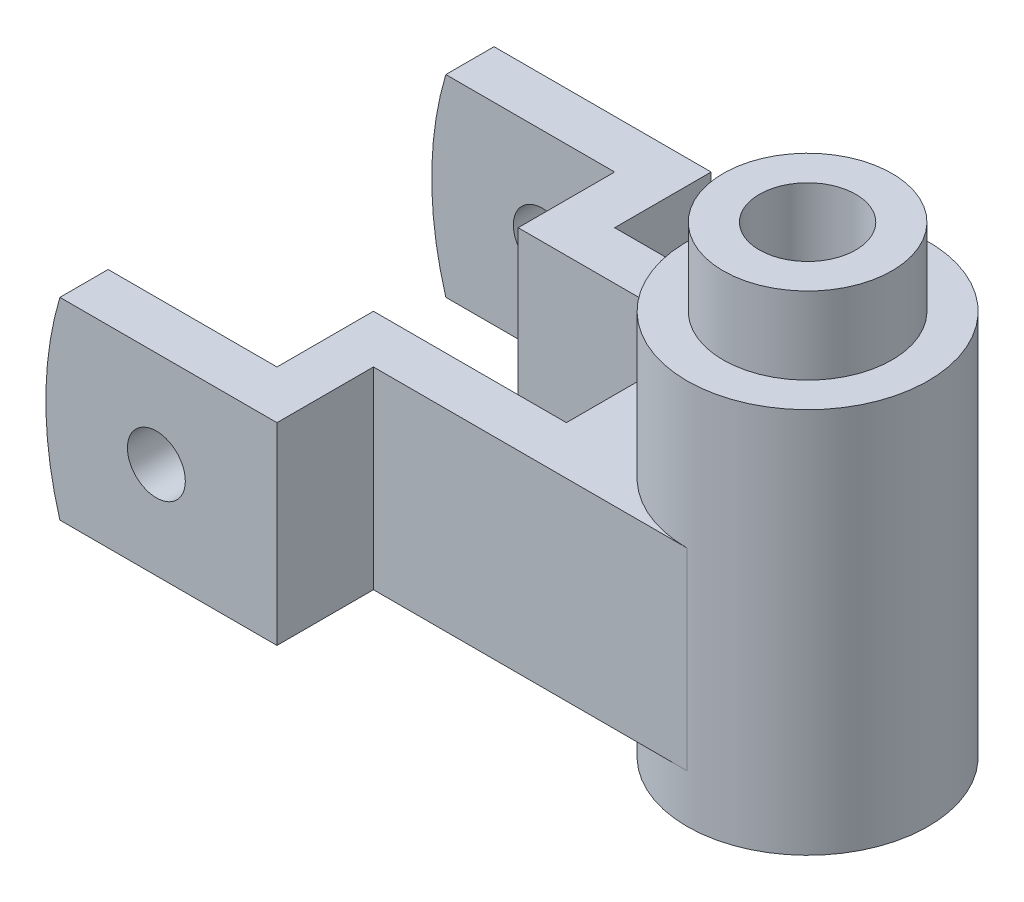
SolidWorks part; units mm, degrees
note: The reader was unsure of these and kept them because the rebuilt part matched: shared geometry of "Sketch2<3>".
ref_plane "Front Plane" through (0, 0, 0) normal (0, 0, 1) x (1, 0, 0)
ref_plane "Top Plane" through (0, 0, 0) normal (0, 1, 0) x (1, 0, 0)
ref_plane "Right Plane" through (0, 0, 0) normal (1, 0, 0) x (0, 0, -1)
sketch "Sketch1" plane through (0, 0, 0) normal (0, 0, 1) x (1, 0, 0)
  line L1 (-77.7569, 20) -> (-122.7569, 20)
  line L3 (-77.7569, -20) -> (-122.7569, -20)
  line L4 (-122.7569, 20) -> (-77.7569, 20)
  line L5 (-77.7569, 20) -> (-77.7569, -20)
  line L6 (-77.7569, -20) -> (-102.7569, -20)
  arc A0 (-122.7569, 20) -> (-122.7569, -20) centre (-55.6749, 0) ccw
  circle A1 centre (-102.7569, 0) radius 6
extrude "Boss-Extrude1" add sketch "Sketch1" along normal blind 10 contours L1 A0 L3 L5 A1
sketch "Sketch2" plane through (0, 20, 0) normal (0, 1, 0) x (1, 0, 0)
  line L0 (-77.7569, 0) -> (-87.7569, 0)
  line L1 (-77.7569, 0) -> (-122.7569, 0) construction
  line L2 (-87.7569, 0) -> (-87.7569, 20)
  line L3 (-77.7569, 0) -> (-77.7569, 10)
  line L9 (-77.7569, 10) -> (-12.7569, 10)
  line L11 (-37.7569, 35) -> (-47.7569, 35)
  line L12 (-47.7569, 35) -> (-47.7569, 20)
  line L13 (-47.7569, 20) -> (-87.7569, 20)
  circle A0 centre (-12.7569, 35) radius 25
  line M10 (-77.7569, 0) -> (-122.7569, 0)
extrude "Boss-Extrude2" add sketch "Sketch2" against normal blind 40 contours A0 L11 L12 L13 L2 L3 L9 M10
extrude "Boss-Extrude3" add sketch "Sketch2<3>" along normal blind 30 and the other way blind 50 contours A0
sketch "Sketch2<3>" plane through (0, 20, 0) normal (0, 1, 0) x (1, 0, 0) same geometry as "Sketch2"
sketch "Sketch3" plane through (0, 50, 0) normal (0, 1, 0) x (1, 0, 0)
  circle A0 centre (-12.7569, 35) radius 17.5
extrude "Boss-Extrude4" add sketch "Sketch3" along normal blind 16
sketch "Sketch4" plane through (0, 66, 0) normal (0, 1, 0) x (1, 0, 0)
  circle A0 centre (-12.7569, 35) radius 10
extrude "Cut-Extrude1" cut sketch "Sketch4" against normal blind 143
ref_plane "Plane1" through (0, 0, -35) normal (0, 0, -1) x (-1, 0, 0)
mirror "Mirror11" about plane through (0, 0, -35) normal (0, 0, -1) of "Boss-Extrude2", "Boss-Extrude1"
mirror "Mirror12" about plane through (0, 0, -35) normal (0, 0, -1) of "Boss-Extrude1"
